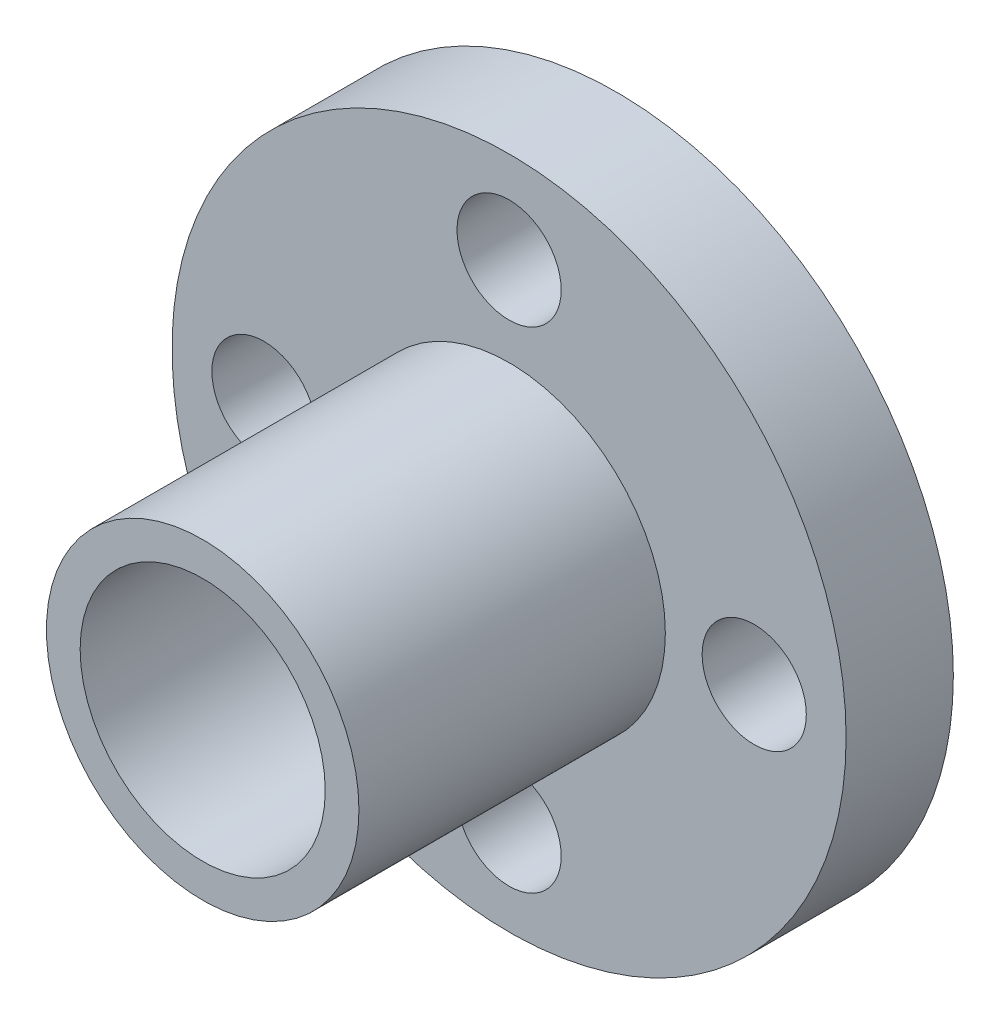
SolidWorks part; units mm, degrees
material "黃銅"
ref_plane "前基準面" through (0, 0, 0) normal (0, 0, 1) x (1, 0, 0)
ref_plane "上基準面" through (0, 0, 0) normal (0, 1, 0) x (1, 0, 0)
ref_plane "右基準面" through (0, 0, 0) normal (1, 0, 0) x (0, 0, -1)
sketch "草圖1" plane through (0, 0, 0) normal (0, 0, 1) x (1, 0, 0)
  circle A0 centre (0, 0) radius 11
  dimension "D1" = 22
extrude "填料-伸長1" add sketch "草圖1" along normal blind 3.5
sketch "草圖2" plane through (0, 0, 3.5) normal (0, 0, 1) x (1, 0, 0)
  circle A0 centre (0, 0) radius 5.1
  dimension "D1" = 10.2
extrude "填料-伸長2" add sketch "草圖2" along normal blind 10
extrude "填料-伸長3" add sketch "草圖2<3>" against normal blind 1.5 from surface starting at face at (11, 0, 0)
sketch "草圖2<3>" plane through (0, 0, 3.5) normal (0, 0, 1) x (1, 0, 0) same geometry as "草圖2"
sketch "草圖3" plane through (0, 0, -1.5) normal (0, 0, -1) x (-1, 0, 0)
  circle A0 centre (0, 0) radius 4
  dimension "D1" = 8
extrude "除料-伸長1" cut sketch "草圖3" against normal through all
hole_wizard "M3 餘隙孔1" positions "草圖4" profile "草圖5" hole size "M3" standard "Ansi Metric" end condition through all
sketch "草圖4" plane through (0, 0, 0) normal (0, 0, -1) x (-1, 0, 0)
  circle A0 centre (0, 0) radius 8 construction
  point P5 (0, 8)
  point P7 (8, 0)
  point P9 (0, -8)
  point P11 (-8, 0)
  dimension "D1" = 16
sketch "草圖5" plane through (8, 0, 0) normal (1, 0, 0) x (0, 1, 0)
  line L0 (0, 0) -> (0, 13.5)
  line L1 (0, 13.5) -> (1.7, 13.5)
  line L2 (1.7, 13.5) -> (1.7, 0)
  line L5 (1.7, 0) -> (0, 0)
  line L11 (0, -6.35) -> (0, 107.95) construction
  dimension "貫穿孔直徑" = 3.4
  dimension "貫穿孔深度" = 13.5
